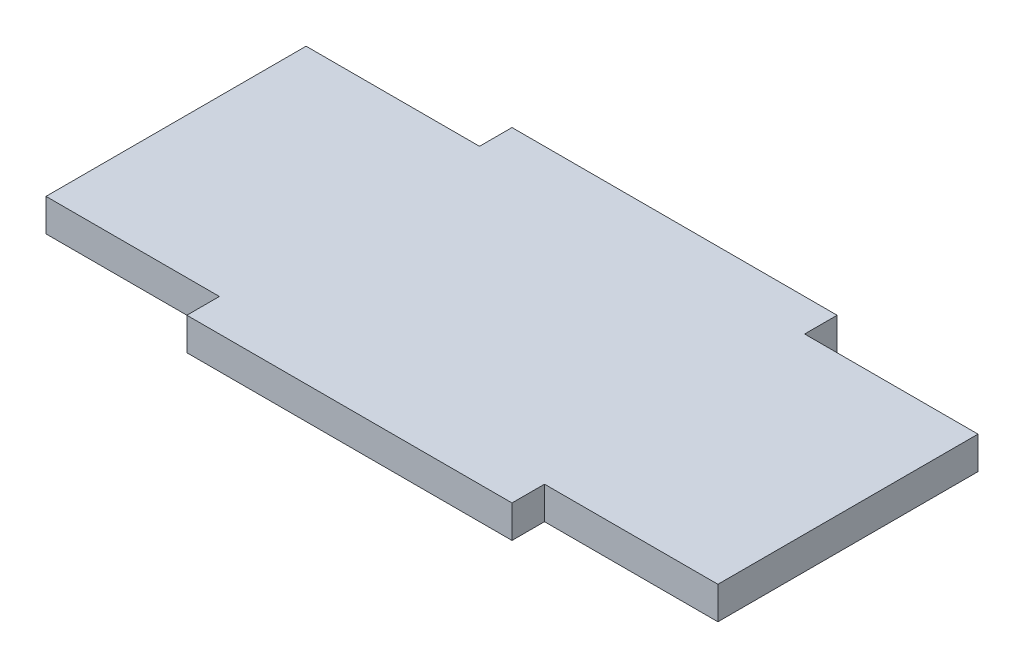
SolidWorks part; units mm, degrees
ref_plane "Alzado" through (0, 0, 0) normal (0, 0, 1) x (1, 0, 0)
ref_plane "Planta" through (0, 0, 0) normal (0, 1, 0) x (1, 0, 0)
ref_plane "Vista lateral" through (0, 0, 0) normal (1, 0, 0) x (0, 0, -1)
sketch "Croquis1" plane through (0, 0, 0) normal (0, 1, 0) x (1, 0, 0)
  line L0 (0, 0) -> (16, 0)
  line L1 (0, 0) -> (0, 24)
  line L2 (0, 24) -> (16, 24)
  line L3 (46, 0) -> (62, 0)
  line L4 (62, 24) -> (62, 0)
  line L5 (46, 27) -> (16, 27)
  line L6 (16, 27) -> (16, 24)
  line L7 (46, 27) -> (46, 24)
  line L8 (46, 24) -> (62, 24)
  line L9 (46, -3) -> (46, 0)
  line L10 (16, -3) -> (16, 0)
  line L11 (46, -3) -> (16, -3)
  dimension "D1" = 62
  dimension "D2" = 24
  dimension "D3" = 30
extrude "Saliente-Extruir1" add sketch "Croquis1" along normal blind 3
